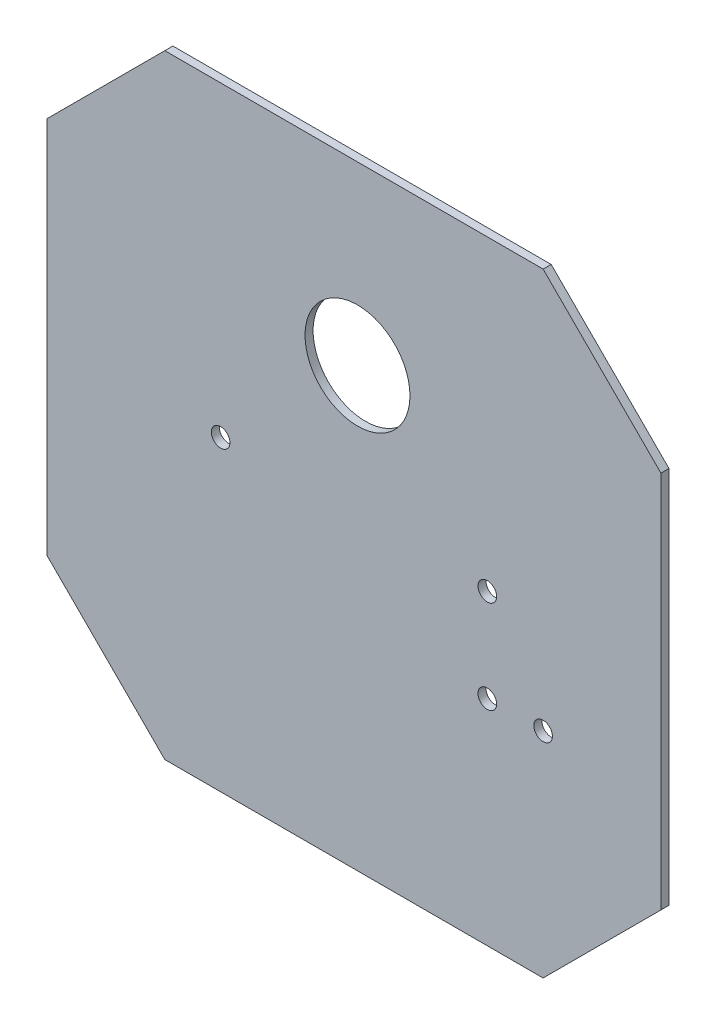
SolidWorks part; units mm, degrees
material "PVC Rigid"
ref_plane "Front Plane" through (0, 0, 0) normal (0, 0, 1) x (1, 0, 0)
ref_plane "Top Plane" through (0, 0, 0) normal (0, 1, 0) x (1, 0, 0)
ref_plane "Right Plane" through (0, 0, 0) normal (1, 0, 0) x (0, 0, -1)
sketch "Sketch1" plane through (0, 0, 0) normal (0, 0, 1) x (1, 0, 0)
  line L0 (-29.649, 62.0347) -> (-29.649, 1.0347)
  line L1 (-10.649, 81.0347) -> (-29.649, 62.0347)
  line L2 (-29.649, 1.0347) -> (-10.649, -17.9653)
  line L3 (50.351, -17.9653) -> (69.351, 1.0347)
  line L4 (69.351, 62.0347) -> (50.351, 81.0347)
  line L5 (-10.649, -17.9653) -> (50.351, -17.9653)
  line L6 (69.351, 1.0347) -> (69.351, 62.0347)
  line L7 (50.351, 81.0347) -> (-10.649, 81.0347)
  circle A0 centre (-1.649, 31.5347) radius 1.5
  circle A1 centre (41.351, 31.5347) radius 1.5
  circle A2 centre (41.351, 16.5347) radius 1.5
  circle A3 centre (50.351, 16.5347) radius 1.5
extrude "Boss-Extrude1" add sketch "Sketch1" along normal blind 1.3
sketch "Sketch3" plane through (0, 0, 1.3) normal (0, 0, 1) x (1, 0, 0)
  circle A0 centre (20.4201, 52.6054) radius 8.4606
extrude "Cut-Extrude1" cut sketch "Sketch3" against normal blind 20
